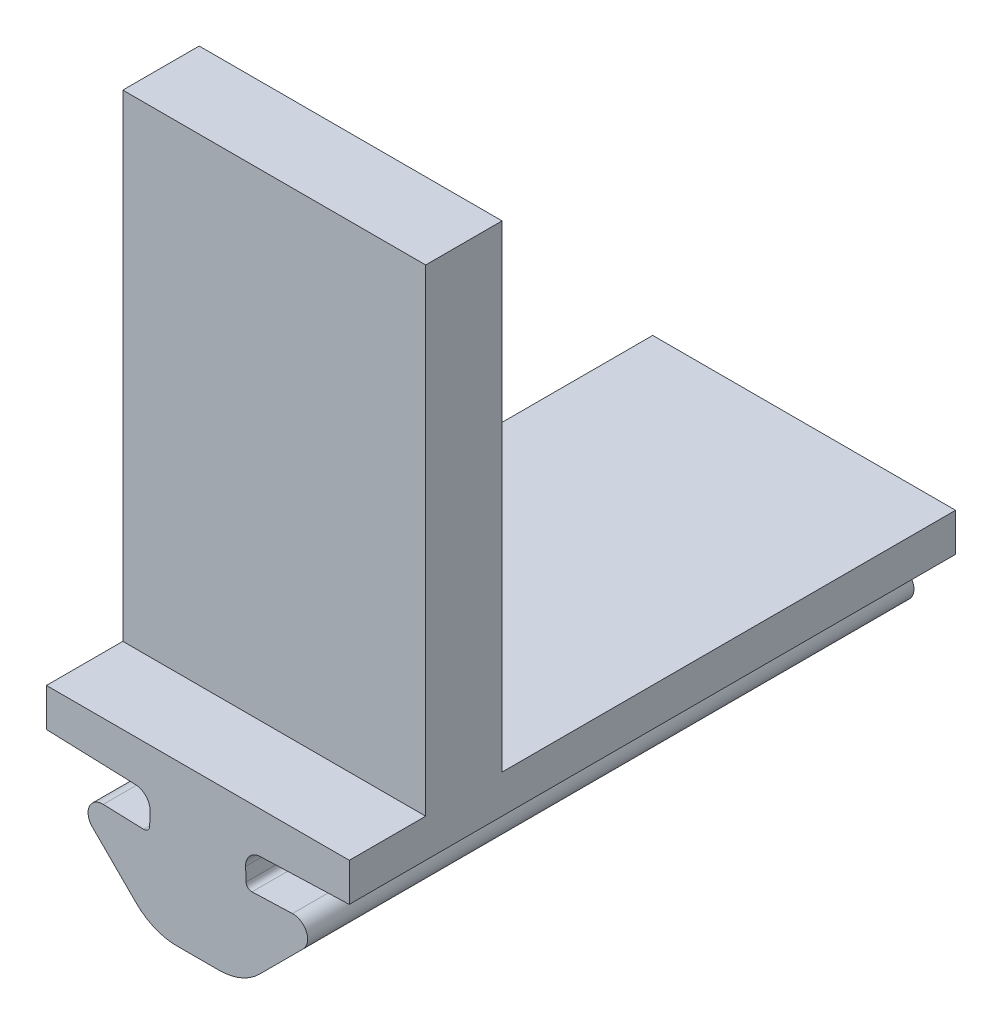
SolidWorks part; units mm, degrees
ref_plane "Front Plane" through (0, 0, 0) normal (0, 0, 1) x (1, 0, 0)
ref_plane "Top Plane" through (0, 0, 0) normal (0, 1, 0) x (1, 0, 0)
ref_plane "Right Plane" through (0, 0, 0) normal (1, 0, 0) x (0, 0, -1)
sketch "Sketch2" plane through (0, 0, 0) normal (0, 0, 1) x (1, 0, 0)
  line L1 (-50.3756, 45.6099) -> (-50.3512, 46.3094)
  line L2 (-50.6859, 45.3205) -> (-52.8037, 45.3945)
  line L6 (-55.7809, 47.2995) -> (-51.1228, 47.1369)
  line L7 (-51.0743, 41.7794) -> (-53.3751, 44.0803)
  line L8 (-47.8507, 40.9008) -> (-48.9529, 40.9008)
  line L9 (-47.8507, 40.9008) -> (-47.8507, 47.2995)
  line L10 (-47.8507, 47.2995) -> (-55.7809, 47.2995)
  arc A0 (-50.6859, 45.3205) -> (-50.3756, 45.6099) centre (-50.6754, 45.6203) ccw
  arc A7 (-50.3512, 46.3094) -> (-51.1228, 47.1369) centre (-51.1507, 46.3374) ccw
  arc A8 (-52.8037, 45.3945) -> (-53.3751, 44.0803) centre (-52.8306, 44.6248) ccw
  arc A9 (-51.0743, 41.7794) -> (-48.9529, 40.9008) centre (-48.9529, 43.9008) ccw
extrude "Boss-Extrude1" add sketch "Sketch2" along normal blind 31.75
ref_plane "Plane2" through (0, 0, 0) normal (0.7071, -0.7071, 0) x (-0.7071, -0.7071, 0)
ref_plane "Plane3" through (-42.746, 42.746, 0) normal (0.7071, -0.7071, 0) x (-0.7071, -0.7071, 0)
mirror "Mirror2" about plane through (-47.8507, 40.9008, 31.75) normal (-1, 0, 0) of "Boss-Extrude1"
ref_plane "Plane7" through (0, 47.2995, 0) normal (0, 1, 0) x (1, 0, 0)
sketch "Sketch19" plane through (0, 47.2995, 0) normal (0, 1, 0) x (1, 0, 0)
  line L0 (-55.7809, -31.75) -> (-55.7809, 0) construction
  line L1 (-55.7809, 0) -> (-39.9205, 0)
  line L2 (-55.7809, 0) -> (-55.7809, -31.75)
  line L3 (-55.7809, -31.75) -> (-39.9205, -31.75)
  line L4 (-39.9205, 0) -> (-39.9205, -31.75)
  line L5 (-39.9205, -31.75) -> (-39.9205, 0) construction
  line L6 (-39.9205, 0) -> (-55.7809, 0) construction
  dimension "D1" = 0
  dimension "D2" = 31.75
extrude "Boss-Extrude7" add sketch "Sketch19" along normal blind 2
sketch "Sketch23" plane through (0, 49.2995, 0) normal (0, 1, 0) x (1, 0, 0)
  line L0 (-55.7809, 0) -> (-55.7809, -31.75) construction
  line L1 (-55.7809, -23.75) -> (-39.9205, -23.75)
  line L2 (-55.7809, -23.75) -> (-55.7809, -27.75)
  line L3 (-55.7809, -27.75) -> (-39.9205, -27.75)
  line L4 (-39.9205, -23.75) -> (-39.9205, -27.75)
  line L5 (-39.9205, -31.75) -> (-39.9205, 0) construction
  line L6 (-39.9205, 0) -> (-55.7809, 0) construction
  dimension "D1" = 4
  dimension "D2" = 0
  dimension "D3" = 0
  dimension "D4" = 27.75
extrude "Boss-Extrude8" add sketch "Sketch23" along normal blind 25
ref_plane "Plane8" through (-39.9205, 49.2995, 23.75) normal (0, -1, 0) x (-1, 0, 0)
sketch "Sketch24" plane through (0, 0, 23.75) normal (0, 0, -1) x (-1, 0, 0)
  line L0 (39.9205, 74.2995) -> (55.7809, 74.2995) construction
  line L1 (55.7809, 74.2995) -> (55.7809, 49.2995) construction
  circle A0 centre (49.1769, 69.2995) radius 1.25
  dimension "D1" = 2.5
  dimension "D2" = 5
  dimension "D3" = 6.604
extrude "Cut-Extrude1" cut sketch "Sketch24" against normal blind 2.54
